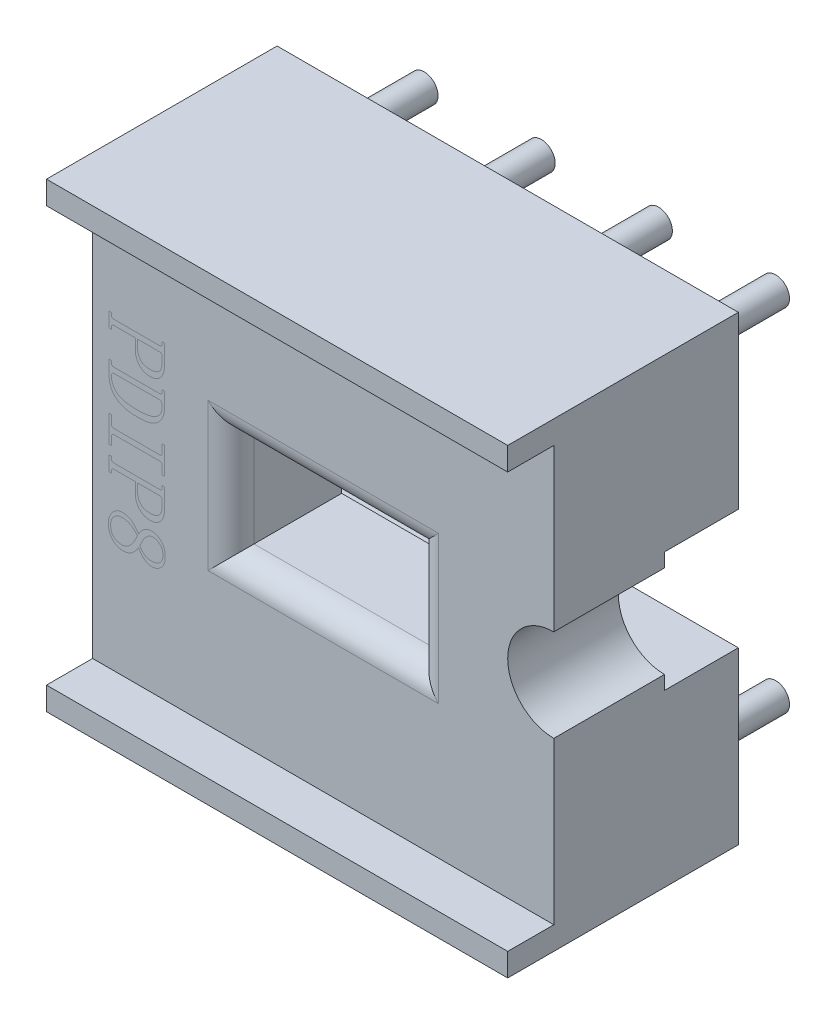
SolidWorks part; units mm, degrees
ref_plane "前视基准面" through (0, 0, 0) normal (0, 0, 1) x (1, 0, 0)
ref_plane "上视基准面" through (0, 0, 0) normal (0, 1, 0) x (1, 0, 0)
ref_plane "右视基准面" through (0, 0, 0) normal (1, 0, 0) x (0, 0, -1)
sketch "草图1" plane through (0, 0, 0) normal (0, 0, 1) x (1, 0, 0)
  line L0 (0, 0) -> (10, 0)
  line L1 (10, 0) -> (10, 4)
  line L2 (10, 10) -> (0, 10)
  line L3 (0, 10) -> (0, 0)
  line L4 (0, 5) -> (10, 5) construction
  line L5 (10, 6) -> (10, 10)
  arc A0 (10, 6) -> (10, 4) centre (10, 5) ccw
  dimension "D3" = 2
  dimension "D1" = 10
  dimension "D2" = 10
extrude "凸台-拉伸1" add sketch "草图1" along normal blind 5
sketch "草图2" plane through (10, 0, 0) normal (1, 0, 0) x (0, 0, -1)
  line L0 (-5, 9.5) -> (-4, 9.5)
  line L1 (-5, 6) -> (-5, 10) construction
  line L3 (-5, 10) -> (0, 10) construction
  line L4 (-5, 5) -> (0, 5) construction
  line L5 (-5, 6) -> (-5, 4) construction
  line L6 (0, 4) -> (0, 6) construction
  line L7 (-5, 0.5) -> (-4, 0.5)
  line L8 (-4, 9.5) -> (-4, 0.5)
  line L9 (-5, 9.5) -> (-5, 0.5)
  line L10 (-1.6, 6.3) -> (-1.6, 3.7)
  line L11 (0, 6) -> (0, 10) construction
  line L12 (-1.6, 6.3) -> (0, 6.3)
  line L13 (-1.6, 3.7) -> (0, 3.7)
  line L14 (0, 6.3) -> (0, 3.7)
  dimension "D1" = 0.5
  dimension "D2" = 1
  dimension "D3" = 1.6
  dimension "D4" = 2.6
extrude "切除-拉伸1" cut sketch "草图2" against normal through all
sketch "草图3" plane through (0, 0, 4) normal (0, 0, 1) x (1, 0, 0)
  line L0 (3, 6.1) -> (3, 3.9)
  line L2 (0, 0.5) -> (10, 0.5) construction
  line L3 (5, 9.5) -> (5, 0.5) construction
  line L4 (0, 9.5) -> (10, 9.5) construction
  line L5 (0, 0.5) -> (0, 9.5) construction
  line L6 (7, 6.1) -> (7, 3.9)
  line L7 (0, 5) -> (9, 5) construction
  line L8 (3, 6.1) -> (7, 6.1)
  line L9 (3, 3.9) -> (7, 3.9)
  arc A0 (10, 6) -> (10, 4) centre (10, 5) ccw construction
  dimension "D1" = 3
  dimension "D2" = 1.1
extrude "切除-拉伸2" cut sketch "草图3" against normal up to next
sketch "草图4" plane through (0, 0, 0) normal (0, 0, -1) x (-1, 0, 0)
  line L0 (-5, 10) -> (-5, 0) construction
  line L1 (-10, 10) -> (0, 10) construction
  line L2 (0, 0) -> (-10, 0) construction
  line L3 (0, 5) -> (-9, 5) construction
  line L4 (0, 6.3) -> (0, 3.7) construction
  arc A0 (-10, 4) -> (-10, 6) centre (-10, 5) ccw construction
  circle A1 centre (-3.73, 8.81) radius 0.3
  circle A2 centre (-1.19, 8.81) radius 0.3
  circle A3 centre (-6.27, 8.81) radius 0.3
  circle A4 centre (-8.81, 8.81) radius 0.3
  circle A5 centre (-8.81, 1.19) radius 0.3
  circle A6 centre (-6.27, 1.19) radius 0.3
  circle A7 centre (-3.73, 1.19) radius 0.3
  circle A8 centre (-1.19, 1.19) radius 0.3
  dimension "D1" = 0.6
  dimension "D2" = 1.27
  dimension "D3" = 7.62
  dimension "D4" = 2
extrude "凸台-拉伸2" add sketch "草图4" along normal blind 2
sketch "草图5" plane through (0, 0, 4) normal (0, 0, 1) x (1, 0, 0)
  line L0 (0.3247, 9.5) -> (0.3247, 0.5) construction
  line L1 (0, 9.5) -> (10, 9.5) construction
  line L2 (0, 0.5) -> (10, 0.5) construction
  text T0 "PDIP8" height 1.2
wrap "包覆1" sketch "草图5" wrap type scribe source sketch "草图5" face at (5, 5, 4)
fillet "圆角1" radius 0.5 4 edges at (3, 5, 4) (5, 3.9, 4) (7, 5, 4) (5, 6.1, 4)
